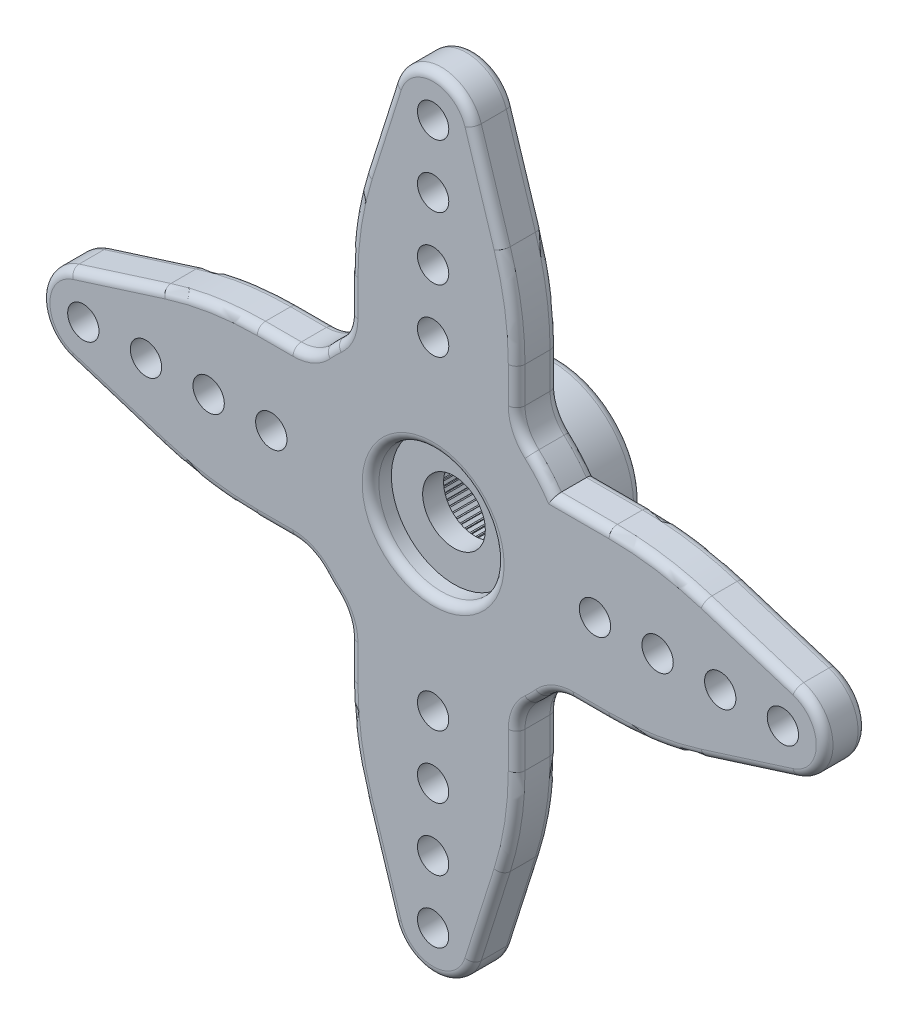
SolidWorks part; units mm, degrees
ref_plane "Ön Düzlem" through (0, 0, 0) normal (0, 0, 1) x (1, 0, 0)
ref_plane "Üst Düzlem" through (0, 0, 0) normal (0, 1, 0) x (1, 0, 0)
ref_plane "Sağ Düzlem" through (0, 0, 0) normal (1, 0, 0) x (0, 0, -1)
sketch "Sketch1" plane through (0, 0, 0) normal (0, 0, 1) x (1, 0, 0)
  line L0 (-4, 10.7446) -> (-4, 5.7446)
  line L1 (4, 10.7446) -> (4, 5.7446)
  line L2 (0, 0) -> (0, 16.75) construction
  line L3 (-4, 5.7446) -> (4, 5.7446) construction
  line L4 (-1.9067, 17.3539) -> (-4, 10.7446)
  line L5 (1.9067, 17.3539) -> (4, 10.7446)
  circle A0 centre (0, 0) radius 7
  circle A1 centre (0, 0) radius 18.75
  circle A2 centre (0, 16.75) radius 2
  circle A3 centre (0, 0) radius 1.5
  dimension "D1" = 37.5
  dimension "D2" = 14
  dimension "D3" = 4
  dimension "D5" = 3
  dimension "D4" = 5
  dimension "D6" = 8
extrude "Boss-Extrude1" add sketch "Sketch1" along normal blind 2 contours A0 A3 | A2 L4 L0 A0 L1 L5 | A2 region at (0, 10.6981, 0) region at (0, 6.802, 0) region at (0, 16.75, 0)
fillet "Fillet1" radius 15 2 edges at (-4, 10.7446, 1) (4, 10.7446, 1)
sketch "Sketch2" plane through (0, 0, 2) normal (0, 0, 1) x (1, 0, 0)
  line L0 (0, 0) -> (0, 18.75) construction
  arc A0 (1.9067, 17.3539) -> (-1.9067, 17.3539) centre (0, 16.75) ccw construction
  circle A1 centre (0, 16.75) radius 0.75
  circle A2 centre (0, 13.75) radius 0.75
  circle A3 centre (0, 10.75) radius 0.75
  circle A4 centre (0, 7.75) radius 0.75
  dimension "D1" = 1.5
  dimension "D2" = 2
  dimension "D3" = 4
extrude "Cut-Extrude1" cut sketch "Sketch2" against normal through all
pattern_circular "CirPattern2" count 4 over 360 about axis through (0, 0, 2) along (0, 0, 1) of "Boss-Extrude1", "Fillet1", "Cut-Extrude1"
fillet "Fillet2" radius 2 7 edges at (4, 5.7446, 1) (-4, 5.7446, 1) (5.7446, -4, 1) (4, -5.7446, 1) (-5.7446, 4, 1) (-4, -5.7446, 1) (-5.7446, -4, 1)
sketch "Sketch3" plane through (0, 0, 2) normal (0, 0, 1) x (1, 0, 0)
  circle A0 centre (0, 0) radius 3
  dimension "D1" = 6
extrude "Cut-Extrude2" cut sketch "Sketch3" against normal blind 1
sketch "Sketch4" plane through (0, 0, 0) normal (0, 0, -1) x (-1, 0, 0)
  circle A0 centre (0, 0) radius 4
  circle A1 centre (0, 0) radius 3
  dimension "D1" = 8
  dimension "D2" = 6
extrude "Boss-Extrude2" add sketch "Sketch4" along normal blind 4
sketch "Sketch5" plane through (0, 0, -4) normal (0, 0, -1) x (-1, 0, 0)
  line L0 (0, 0) -> (0, -4) construction
  line L2 (0.025, -2.8941) -> (-0.025, -2.8941)
  line L3 (0.025, -2.8941) -> (0.025, -3.3941)
  line L4 (0.025, -3.3941) -> (-0.025, -3.3941)
  line L5 (-0.025, -2.8941) -> (-0.025, -3.3941)
  line L6 (0.025, -2.8941) -> (-0.025, -3.3941) construction
  line L7 (0.025, -3.3941) -> (-0.025, -2.8941) construction
  circle A1 centre (0, 0) radius 4 construction
  point P0 (0, -3.1441)
  dimension "D1" = 0.05
  dimension "D2" = 0.5
extrude "Boss-Extrude3" add sketch "Sketch5" against normal up to surface (4 mm away) up to face at (-3, 0, 0)
pattern_circular "CirPattern3" count 80 over 360 about axis through (0, 0, -4) along (0, 0, -1) of "Boss-Extrude3"
fillet "Fillet3" radius 0.4 81 edges at (7.0852, 4, 0) (10.7173, 3.8239, 0) (15.1545, 2.6033, 0) (18.75, 0, 0) (15.1545, -2.6033, 0) (10.7173, -3.8239, 0) (7.567, -4, 0) (5.8917, -4.1743, 0) (4.9497, -4.9497, 0) (4.1743, -5.8917, 0) (4, -7.567, 0) (3.8239, -10.7173, 0) (2.6033, -15.1545, 0) (0, -18.75, 0) (-2.6033, -15.1545, 0) (-3.8239, -10.7173, 0) (-4, -7.567, 0) (-4.1743, -5.8917, 0) (-4.9497, -4.9497, 0) (-5.8917, -4.1743, 0) (-7.567, -4, 0) (-10.7173, -3.8239, 0) (-15.1545, -2.6033, 0) (-18.75, 0, 0) (-15.1545, 2.6033, 0) (-10.7173, 3.8239, 0) (-7.567, 4, 0) (-5.8917, 4.1743, 0) (-4.9497, 4.9497, 0) (-4.1743, 5.8917, 0) (-4, 7.567, 0) (-3.8239, 10.7173, 0) (-2.6033, 15.1545, 0) (0, 18.75, 0) (5.2411, 4.6402, 0) (4.1743, 5.8917, 0) (4, 7.567, 0) (3.8239, 10.7173, 0) (7.0852, 4, 2) (10.7173, 3.8239, 2) (15.1545, 2.6033, 2) (18.75, 0, 2) (15.1545, -2.6033, 2) (10.7173, -3.8239, 2) (7.567, -4, 2) (5.8917, -4.1743, 2) (4.9497, -4.9497, 2) (4.1743, -5.8917, 2) (4, -7.567, 2) (3.8239, -10.7173, 2) (2.6033, -15.1545, 2) (0, -18.75, 2) (-2.6033, -15.1545, 2) (-3.8239, -10.7173, 2) (-4, -7.567, 2) (-4.1743, -5.8917, 2) (-4.9497, -4.9497, 2) (-5.8917, -4.1743, 2) (-7.567, -4, 2) (-10.7173, -3.8239, 2) (-15.1545, -2.6033, 2) (-18.75, 0, 2) (-15.1545, 2.6033, 2) (-10.7173, 3.8239, 2) (-7.567, 4, 2) (-5.8917, 4.1743, 2) (-4.9497, 4.9497, 2) (-4.1743, 5.8917, 2) (-4, 7.567, 2) (-3.8239, 10.7173, 2) (-2.6033, 15.1545, 2) (0, 18.75, 2) (5.2411, 4.6402, 2) (4.1743, 5.8917, 2) (4, 7.567, 2) (3.8239, 10.7173, 2) (2.6033, 15.1545, 0) (2.6033, 15.1545, 2) (3, 0, 2) (-4, 0, -4) (4, 0, 0)
